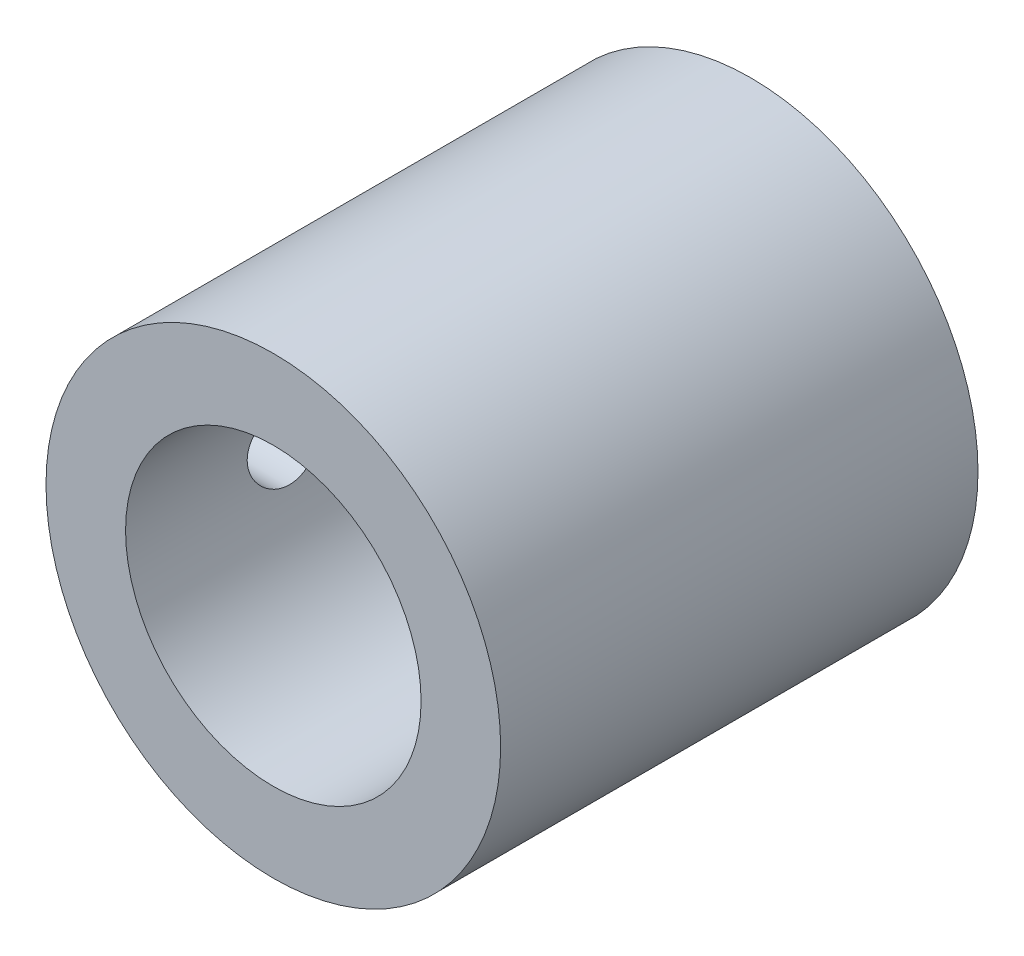
SolidWorks part; units mm, degrees
material "3.1355 (EN-AW 2024)"
ref_plane "Front" through (0, 0, 0) normal (0, 0, 1) x (1, 0, 0)
ref_plane "Top" through (0, 0, 0) normal (0, 1, 0) x (1, 0, 0)
ref_plane "Right" through (0, 0, 0) normal (1, 0, 0) x (0, 0, -1)
sketch "Эскиз1" plane through (0, 0, 0) normal (0, 0, 1) x (1, 0, 0)
  circle A0 centre (0, 0) radius 10
  dimension "D1" = 20
extrude "Бобышка-Вытянуть1" add sketch "Эскиз1" along normal blind 21
sketch "Эскиз2" plane through (0, 0, 21) normal (0, 0, 1) x (1, 0, 0)
  circle A0 centre (0, 0) radius 6.5
  dimension "D1" = 13
extrude "Вырез-Вытянуть1" cut sketch "Эскиз2" against normal blind 15
sketch "Эскиз3" plane through (0, 0, 0) normal (0, 1, 0) x (1, 0, 0)
  line L0 (-10, -21) -> (-10, -16) construction
  dimension "D1" = 5
ref_plane "Плоскость1" through (-10, 0, 0) normal (1, 0, 0) x (0, 0, -1)
hole_wizard "Отверстие обработанное метчиком M4x0.71" positions "Эскиз5" profile "Эскиз4" tap size "M4x0.7" standard "Ansi Metric"
sketch "Эскиз5" plane through (-10, 0, 0) normal (1, 0, 0) x (0, 0, -1)
  line L0 (-21, 0) -> (-16, 0) construction
  point P0 (-14, 0)
sketch "Эскиз4" plane through (-10, 0, 14) normal (0, 1, 0) x (0, 0, 1)
  line L0 (0, 0) -> (0, 5.9914)
  line L1 (0, 5.9914) -> (1.65, 5)
  line L2 (1.65, 5) -> (1.65, 0)
  line L5 (1.65, 0) -> (0, 0)
  line L10 (0, 5.9914) -> (-1.65, 5) construction
  line L11 (0, -6.35) -> (0, 107.95) construction
  dimension "Диаметр сверла" = 3.3
  dimension "Глубина сверла" = 5
  dimension "Угол заточки сверла" = 118
cosmetic thread "Отверстие резьбы1"
sketch "Эскиз7" plane through (0, 0, 0) normal (0, 0, -1) x (-1, 0, 0)
  line L0 (-6, 0) -> (0, 0) construction
  line L1 (0, 0) -> (-4.2426, 4.2426) construction
  line L2 (0, 0) -> (4.2426, 4.2426) construction
  line L3 (0, 0) -> (4.2426, -4.2426) construction
  line L4 (0, 0) -> (-4.2426, -4.2426) construction
  circle A0 centre (0, 0) radius 6 construction
  point P11 (0, 0)
  dimension "D1" = 12
  dimension "D2" = 45
  dimension "D3" = 4
hole_wizard "Отверстие обработанное метчиком M3x0.51" positions "Эскиз9" profile "Эскиз8" tap size "M3x0.5" standard "Ansi Metric" end condition up to next
sketch "Эскиз9" plane through (0, 0, 0) normal (0, 0, -1) x (-1, 0, 0)
  point P0 (-4.2426, 4.2426)
  point P3 (4.2426, 4.2426)
  point P6 (4.2426, -4.2426)
  point P9 (-4.2426, -4.2426)
sketch "Эскиз8" plane through (4.2426, 4.2426, 0) normal (1, 0, 0) x (0, 1, 0)
  line L0 (0, 0) -> (0, 6)
  line L1 (0, 6) -> (1.25, 6)
  line L2 (1.25, 6) -> (1.25, 0)
  line L5 (1.25, 0) -> (0, 0)
  line L11 (0, -6.35) -> (0, 107.95) construction
  dimension "Диаметр проходного сверла" = 2.5
  dimension "Глубина проходного сверла" = 6
cosmetic thread "Отверстие резьбы2"
cosmetic thread "Отверстие резьбы3"
cosmetic thread "Отверстие резьбы4"
cosmetic thread "Отверстие резьбы5"
